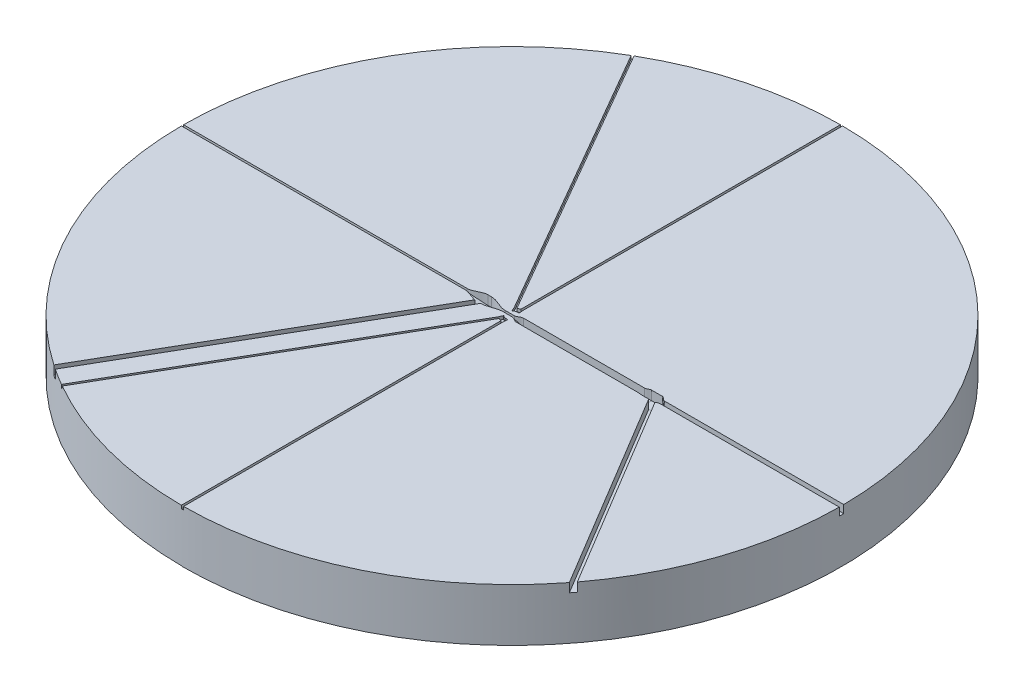
SolidWorks part; units mm, degrees
ref_plane "Front Plane" through (0, 0, 0) normal (0, 0, 1) x (1, 0, 0)
ref_plane "Top Plane" through (0, 0, 0) normal (0, 1, 0) x (1, 0, 0)
ref_plane "Right Plane" through (0, 0, 0) normal (1, 0, 0) x (0, 0, -1)
sketch "Sketch1" plane through (0, 0, 0) normal (0, 1, 0) x (1, 0, 0)
  circle A0 centre (0, 0) radius 12.5
extrude "Boss-Extrude1" add sketch "Sketch1" against normal blind 2
sketch "Sketch2" plane through (0, -2, 0) normal (0, -1, 0) x (-1, 0, 0)
  line L1 (0, 14) -> (14, 14)
  line L2 (0, 14) -> (0, -14)
  line L3 (0, -14) -> (14, -14)
  line L4 (14, 14) -> (14, -14)
  point P4 (0, 0)
extrude "Cut-Extrude1" cut sketch "Sketch2" against normal blind 3.01 from offset 3
sketch "Sketch4" plane through (0, 0, 0) normal (-1, 0, 0) x (0, 0, 1)
  line L1 (-0.04, 0.121) -> (0.04, 0.121)
  line L2 (-0.04, 0.121) -> (-0.04, -0.121)
  line L3 (-0.04, -0.121) -> (0.04, -0.121)
  line L4 (0.04, 0.121) -> (0.04, -0.121)
  line L5 (-0.04, 0.121) -> (0.04, -0.121) construction
  line L6 (-0.04, -0.121) -> (0.04, 0.121) construction
  point P0 (0, 0)
extrude "Cut-Extrude2" cut sketch "Sketch4" against normal blind 0.05
ref_plane "Plane1" through (0.3, 0, 0) normal (-1, 0, 0) x (0, 0, 1)
sketch "Sketch5" plane through (0.3, 0, 0) normal (-1, 0, 0) x (0, 0, 1)
  line L1 (-0.135, 0.291) -> (0.135, 0.291)
  line L2 (-0.135, 0.291) -> (-0.135, -0.291)
  line L3 (-0.135, -0.291) -> (0.135, -0.291)
  line L4 (0.135, 0.291) -> (0.135, -0.291)
  line L5 (-0.135, 0.291) -> (0.135, -0.291) construction
  line L6 (-0.135, -0.291) -> (0.135, 0.291) construction
  point P1 (0, 0)
extrude "Cut-Extrude3" cut sketch "Sketch5" against normal blind 5
sketch "Sketch7" plane through (0.05, 0, 0) normal (-1, 0, 0) x (0, 0, 1)
  line L1 (-0.04, 0) -> (0.04, 0)
  line L2 (-0.04, 0) -> (-0.04, -0.121)
  line L3 (-0.04, -0.121) -> (0.04, -0.121)
  line L4 (0.04, 0) -> (0.04, -0.121)
sketch "Sketch8" plane through (0.3, 0, 0) normal (-1, 0, 0) x (0, 0, 1)
  line L1 (-0.135, 0) -> (0.135, 0)
  line L2 (-0.135, 0) -> (-0.135, -0.291)
  line L3 (-0.135, -0.291) -> (0.135, -0.291)
  line L4 (0.135, 0) -> (0.135, -0.291)
loft "Cut-Loft3" cut profiles "Sketch7", "Sketch8" start constraint normal to profile start tangent length 1 end constraint normal to profile end tangent length 1 connector at (0.05, 0, 0.04) connector at (0.3, 0, 0.135)
ref_point "Point1"
ref_axis "Axis1" through (0, 0, 0) along (1, 0, 0)
ref_plane "Plane2" through (5.3, 0, 0) normal (-1, 0, 0) x (0, 0, 1)
sketch "Sketch9" plane through (0, 0, 0) normal (0, 1, 0) x (1, 0, 0)
  line L0 (5.3, 0) -> (10.5, -8.6603)
  line L1 (5.3, 0.135) -> (5.3, -0.135) construction
ref_plane "Plane3" through (5.3, 0, 0) normal (0.5148, 0, 0.8573) x (0.8573, 0, -0.5148)
ref_plane "Plane4" through (1.4559, 0, 2.4248) normal (0.5148, 0, 0.8573) x (0.8573, 0, -0.5148)
sketch "Sketch15" plane through (1.4559, 0, 2.4248) normal (0.5148, 0, 0.8573) x (0.8573, 0, -0.5148)
  line L1 (4.4974, -0.3363) -> (4.6976, -0.3363)
  line L2 (4.4974, -0.3363) -> (4.4974, 0)
  line L3 (4.4974, 0) -> (4.6976, 0)
  line L4 (4.6976, -0.3363) -> (4.6976, 0)
  line L5 (4.4974, -0.3363) -> (4.6976, 0) construction
  line L6 (4.4974, 0) -> (4.6976, -0.3363) construction
  point P0 (4.5975, -0.1682)
extrude "Cut-Extrude4" cut sketch "Sketch15" along normal blind 10
sketch "Sketch20" plane through (5.3, 0, 0) normal (-1, 0, 0) x (0, 0, 1)
  line L1 (-0.2, 0) -> (0.15, 0)
  line L2 (-0.2, 0) -> (-0.2, -0.35)
  line L3 (-0.2, -0.35) -> (0.15, -0.35)
  line L4 (0.15, 0) -> (0.15, -0.35)
  line L5 (-0.2, 0) -> (0.15, -0.35) construction
  line L6 (-0.2, -0.35) -> (0.15, 0) construction
  point P0 (-0.025, -0.175)
extrude "Cut-Extrude7" cut sketch "Sketch20" against normal blind 0.2 and the other way blind 0.2
ref_plane "Plane5" through (4.9, 0, 0) normal (-1, 0, 0) x (0, 0, 1)
sketch "Sketch21" plane through (4.9, 0, 0) normal (-1, 0, 0) x (0, 0, 1)
  line L1 (-0.135, 0) -> (0.135, 0)
  line L2 (-0.135, 0) -> (-0.135, -0.291)
  line L3 (-0.135, -0.291) -> (0.135, -0.291)
  line L4 (0.135, 0) -> (0.135, -0.291)
sketch "Sketch22" plane through (5.1, 0, 0) normal (1, 0, 0) x (0, 0, -1)
  line L1 (-0.15, 0) -> (0.2, 0)
  line L2 (-0.15, 0) -> (-0.15, -0.35)
  line L3 (-0.15, -0.35) -> (0.2, -0.35)
  line L4 (0.2, 0) -> (0.2, -0.35)
loft "Cut-Loft4" cut profiles "Sketch22", "Sketch21" start constraint normal to profile start tangent length 1 end constraint normal to profile end tangent length 1 connector at (5.1, 0, 0.15) connector at (4.9, 0, 0.135)
ref_plane "Plane6" through (5.7, 0, 0) normal (-1, 0, 0) x (0, 0, 1)
sketch "Sketch23" plane through (5.7, 0, 0) normal (-1, 0, 0) x (0, 0, 1)
  line L0 (-0.04, 0) -> (-12.5, 0) construction
  line L1 (-0.085, 0) -> (0.085, 0)
  line L2 (-0.085, 0) -> (-0.085, -0.3)
  line L3 (-0.085, -0.3) -> (0.085, -0.3)
  line L4 (0.085, 0) -> (0.085, -0.3)
sketch "Sketch24" plane through (5.5, 0, 0) normal (-1, 0, 0) x (0, 0, 1)
  line L1 (0.15, 0) -> (-0.2, 0)
  line L2 (0.15, 0) -> (0.15, -0.35)
  line L3 (0.15, -0.35) -> (-0.2, -0.35)
  line L4 (-0.2, 0) -> (-0.2, -0.35)
loft "Cut-Loft5" cut profiles "Sketch24", "Sketch23" start constraint normal to profile start tangent length 1 end constraint normal to profile end tangent length 1 connector at (5.5, 0, -0.2) connector at (5.7, 0, -0.085)
extrude "Cut-Extrude8" cut sketch "Sketch23<2>" against normal blind 8
sketch "Sketch23<2>" plane through (5.7, 0, 0) normal (-1, 0, 0) x (0, 0, 1) same geometry as "Sketch23"
mirror "Mirror1" [suppressed] about plane through (0, 0, 0) normal (1, 0, 0) of bodies 113
ref_plane "Plane7" through (0, 0, 0.212) normal (0, 0, -1) x (-1, 0, 0)
sketch "Sketch26" plane through (0, 0, 0.212) normal (0, 0, -1) x (-1, 0, 0)
  line L1 (-0.04, 0) -> (0.04, 0)
  line L2 (-0.04, 0) -> (-0.04, -0.121)
  line L3 (-0.04, -0.121) -> (0.04, -0.121)
  line L4 (0.04, 0) -> (0.04, -0.121)
  line L5 (-0.04, 0) -> (0.04, -0.121) construction
  line L6 (-0.04, -0.121) -> (0.04, 0) construction
  point P0 (0, -0.0605)
extrude "Cut-Extrude9" cut sketch "Sketch26" against normal blind 13
sketch "Sketch27" plane through (0, 0, 0) normal (0, 1, 0) x (1, 0, 0)
  line L0 (0, 0) -> (-1.6943, -2.9346)
  line L1 (0.0276, -0.212) -> (-0.0276, -0.212) construction
  line L2 (0.0625, -0.3002) -> (-0.0625, -0.3002)
  line L3 (0.0625, -0.3002) -> (0.0625, -0.212)
  line L4 (0.0625, -0.212) -> (-0.0625, -0.212)
  line L5 (-0.0625, -0.3002) -> (-0.0625, -0.212)
  line L6 (0.0625, -0.3002) -> (-0.0625, -0.212) construction
  line L7 (0.0625, -0.212) -> (-0.0625, -0.3002) construction
  point P3 (0, -0.2561)
ref_plane "Plane8" through (0, 0, 0) normal (-0.5, 0, 0.866) x (0.866, 0, 0.5)
ref_point "Point2"
ref_plane "Plane9" through (-0.1074, 0, 0.1861) normal (-0.5, 0, 0.866) x (0.866, 0, 0.5)
sketch "Sketch28" plane through (-0.1074, 0, 0.1861) normal (-0.5, 0, 0.866) x (0.866, 0, 0.5)
  line L1 (-0.04, 0) -> (0.04, 0)
  line L2 (-0.04, 0) -> (-0.04, -0.121)
  line L3 (-0.04, -0.121) -> (0.04, -0.121)
  line L4 (0.04, 0) -> (0.04, -0.121)
  line L5 (-0.04, 0) -> (0.04, -0.121) construction
  line L6 (-0.04, -0.121) -> (0.04, 0) construction
  point P0 (0, -0.0605)
extrude "Cut-Extrude10" cut sketch "Sketch28" along normal blind 13
mirror "Mirror2" about plane through (0, 0, 0) normal (0, 0, 1) of "Cut-Extrude10", "Cut-Extrude9"
sketch "Sketch29" plane through (0, -0.121, 0) normal (0, 1, 0) x (1, 0, 0)
  line L0 (-0.0625, -0.212) -> (-0.1584, -0.1566)
  line L1 (-1.7215, 0.7458) -> (1.5066, -1.1179) construction
  line L2 (-0.1584, -0.1566) -> (-0.2204, -0.3017)
  line L3 (-6.2846, -10.8053) -> (-0.1421, -0.1661) construction
  line L4 (-0.2204, -0.3017) -> (-0.1511, -0.3417)
  line L5 (-6.2153, -10.8453) -> (-0.0728, -0.2061) construction
  line L6 (-0.1511, -0.3417) -> (-0.04, -0.3752)
  line L7 (-0.04, -12.4999) -> (-0.04, -0.212) construction
  line L8 (-0.04, -0.3752) -> (0.04, -0.3752)
  line L9 (0.04, -12.4999) -> (0.04, -0.212) construction
  line L10 (0.04, -0.3752) -> (0.0554, -0.212)
  line L11 (0.0625, -0.212) -> (-0.0625, -0.212) construction
  line L12 (0.0554, -0.212) -> (-0.0625, -0.212)
extrude "Cut-Extrude11" cut sketch "Sketch29" along normal blind 0.121
mirror "Mirror3" about plane through (0, 0, 0) normal (0, 0, 1) of "Cut-Extrude11"
sketch "Sketch32" plane through (0, 0, 0) normal (1, 0, 0) x (0, 0, -1)
  line L1 (-0.04, 0) -> (0.04, 0)
  line L2 (-0.04, 0) -> (-0.04, -0.121)
  line L3 (-0.04, -0.121) -> (0.04, -0.121)
  line L4 (0.04, 0) -> (0.04, -0.121)
extrude "Cut-Extrude12" cut sketch "Sketch32" against normal blind 14
ref_plane "Plane10" through (-1, 0, 0) normal (1, 0, 0) x (0, 0, -1)
ref_point "Point3"
ref_plane "Plane11" through (-0.25, 0, 0.433) normal (-0.5, 0, 0.866) x (0.866, 0, 0.5)
sketch "Sketch34" plane through (-0.25, 0, 0.433) normal (-0.5, 0, 0.866) x (0.866, 0, 0.5)
  line L1 (-0.966, 0.336) -> (-0.766, 0.336)
  line L2 (-0.966, 0.336) -> (-0.966, -0.336)
  line L3 (-0.966, -0.336) -> (-0.766, -0.336)
  line L4 (-0.766, 0.336) -> (-0.766, -0.336)
  line L5 (-0.966, 0.336) -> (-0.766, -0.336) construction
  line L6 (-0.966, -0.336) -> (-0.766, 0.336) construction
  point P0 (-0.866, 0)
extrude "Cut-Extrude13" cut sketch "Sketch34" along normal blind 12
ref_plane "Plane12" through (-0.3, 0, 0) normal (1, 0, 0) x (0, 0, -1)
sketch "Sketch35" plane through (-0.3, 0, 0) normal (1, 0, 0) x (0, 0, -1)
  line L1 (-0.04, 0) -> (0.04, 0)
  line L2 (-0.04, 0) -> (-0.04, -0.121)
  line L3 (-0.04, -0.121) -> (0.04, -0.121)
  line L4 (0.04, 0) -> (0.04, -0.121)
sketch "Sketch36" plane through (-1, 0, 0) normal (1, 0, 0) x (0, 0, -1)
  line L1 (0.2282, -0.35) -> (-0.1956, -0.35)
  line L2 (0.2282, -0.35) -> (0.2282, 0)
  line L3 (0.2282, 0) -> (-0.1956, 0)
  line L4 (-0.1956, -0.35) -> (-0.1956, 0)
  line L5 (0, 0) -> (-8.6603, 0) construction
loft "Cut-Loft6" cut profiles "Sketch35", "Sketch36" start constraint normal to profile start tangent length 1 end constraint normal to profile end tangent length 1 connector at (-0.3, 0, 0.04) connector at (-1, 0, 0.1956)
ref_plane "Plane13" through (-1.14, 0, 0) normal (1, 0, 0) x (0, 0, -1)
sketch "Sketch37" plane through (-1.14, 0, 0) normal (1, 0, 0) x (0, 0, -1)
  line L0 (0.3752, 0) -> (0.212, 0) construction
  line L1 (-0.1956, -0.35) -> (0.2282, -0.35)
  line L2 (-0.1956, -0.35) -> (-0.1956, 0)
  line L3 (-0.1956, 0) -> (0.2282, 0)
  line L4 (0.2282, -0.35) -> (0.2282, 0)
  line L5 (0.2282, -0.35) -> (0.2282, 0) construction
extrude "Cut-Extrude15" cut sketch "Sketch37" against normal up to surface from surface up to plane "Plane13" starting at plane "Plane10"
ref_plane "Plane14" through (-1.74, 0, 0) normal (1, 0, 0) x (0, 0, -1)
sketch "Sketch38" plane through (-1.74, 0, 0) normal (1, 0, 0) x (0, 0, -1)
  line L1 (-0.04, 0) -> (0.04, 0)
  line L2 (-0.04, 0) -> (-0.04, -0.121)
  line L3 (-0.04, -0.121) -> (0.04, -0.121)
  line L4 (0.04, 0) -> (0.04, -0.121)
loft "Cut-Loft7" cut profiles "Sketch37<2>", "Sketch38" start constraint normal to profile start tangent length 1 end constraint normal to profile end tangent length 1 connector at (-1.14, 0, 0.1956) connector at (-1.74, 0, 0.04)
sketch "Sketch37<2>" plane through (-1.14, 0, 0) normal (1, 0, 0) x (0, 0, -1) same geometry as "Sketch37"
